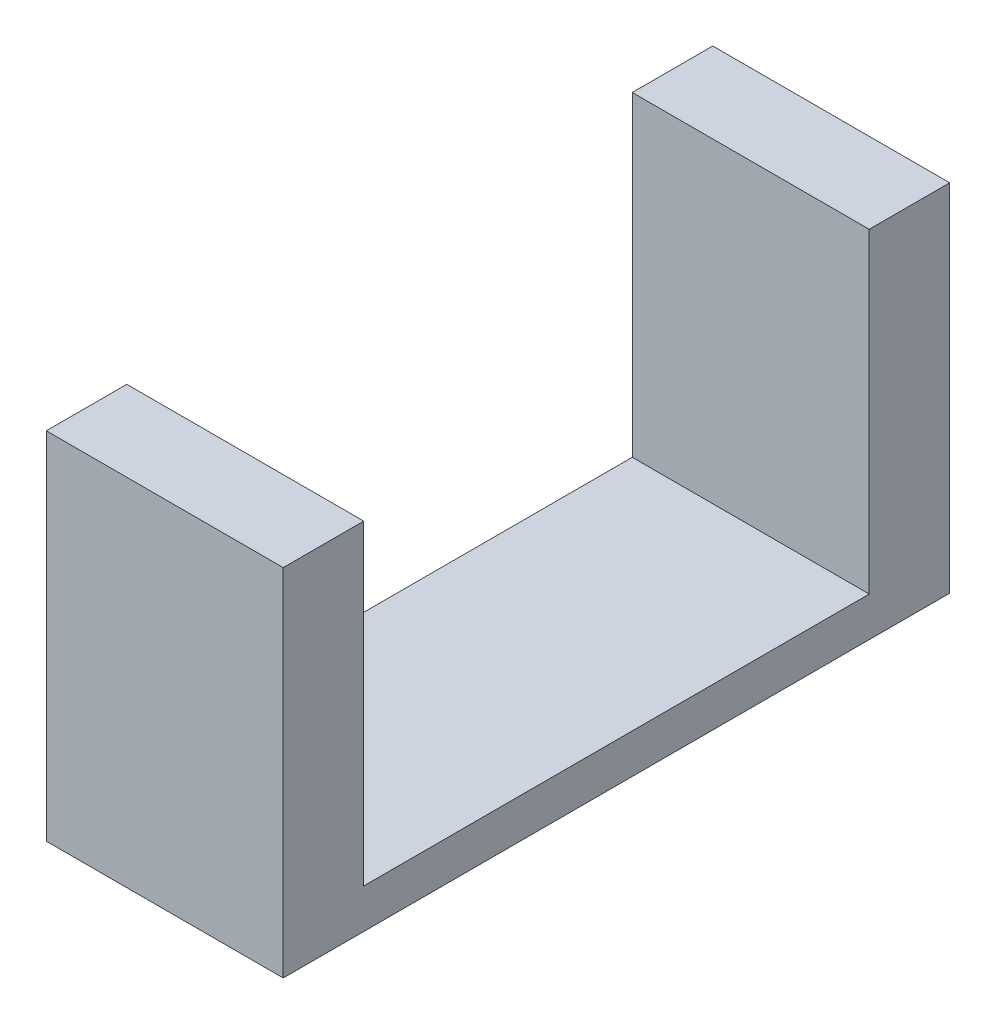
SolidWorks part; units mm, degrees
material "ABS"
ref_plane "Front Plane" through (0, 0, 0) normal (0, 0, 1) x (1, 0, 0)
ref_plane "Top Plane" through (0, 0, 0) normal (0, 1, 0) x (1, 0, 0)
ref_plane "Right Plane" through (0, 0, 0) normal (1, 0, 0) x (0, 0, -1)
sketch "Sketch1" plane through (0, 0, 0) normal (0, 1, 0) x (1, 0, 0)
  line L0 (-9.525, 20.32) -> (9.525, 20.32)
  line L1 (-9.525, -26.7921) -> (9.525, -26.7921)
  line L2 (-9.525, -26.7921) -> (-9.525, 26.7921)
  line L3 (-9.525, 26.7921) -> (9.525, 26.7921)
  line L4 (9.525, -26.7921) -> (9.525, 26.7921)
  line L5 (-9.525, -26.7921) -> (9.525, 26.7921) construction
  line L6 (-9.525, 26.7921) -> (9.525, -26.7921) construction
  line L7 (-9.525, -20.32) -> (9.525, -20.32)
  line L8 (0, -26.7921) -> (0, -20.32) construction
  line L9 (0, 26.7921) -> (0, 20.32) construction
  point P0 (0, 0)
  dimension "D1" = 40.64
  dimension "D2" = 19.05
extrude "Boss-Extrude1" add sketch "Sketch1" along normal blind 3.175 contours L2 L7 L4 L0 | L0 L4 L3 L2 | L7 L2 L1 L4 region at (0, 0, -23.556) region at (0, 0, 0) region at (0, 0, 23.556)
extrude "Boss-Extrude2" add sketch "Sketch1<3>" along normal blind 28.575 contours L0 L4 L3 L2 | L7 L2 L1 L4 region at (0, 0, -23.556) region at (0, 0, 23.556)
sketch "Sketch1<3>" plane through (0, 0, 0) normal (0, 1, 0) x (1, 0, 0) same geometry as "Sketch1"
